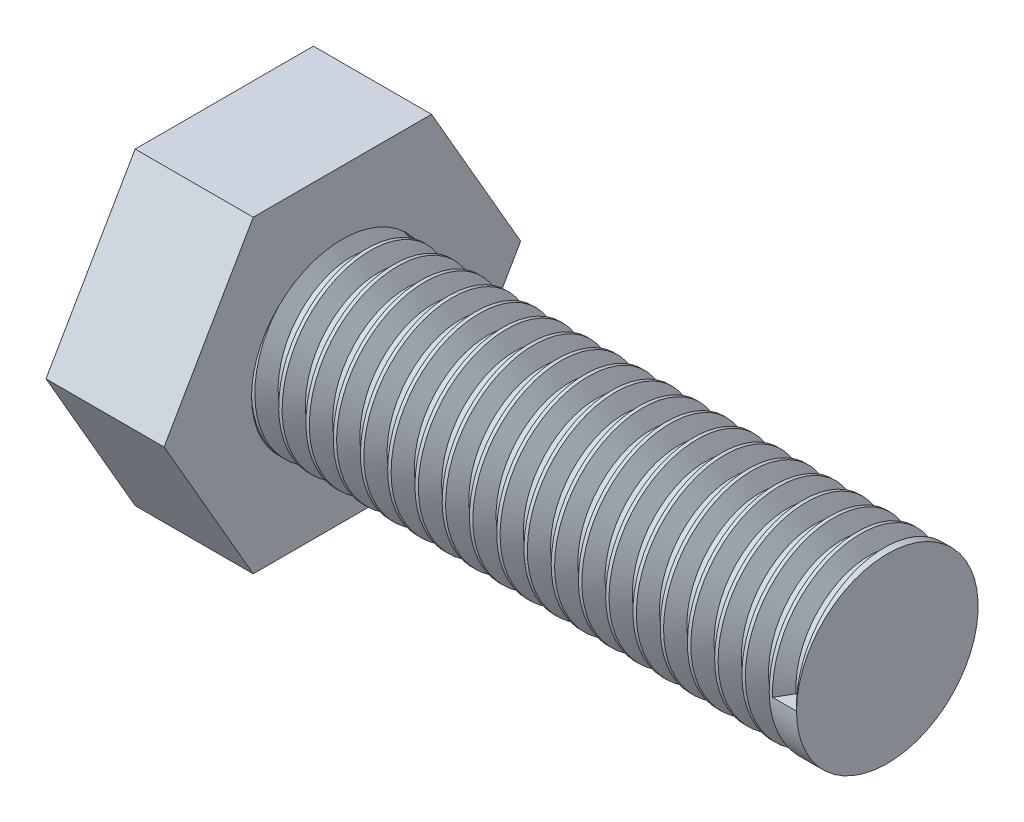
SolidWorks part; units mm, degrees
ref_plane "Front Plane" through (0, 0, 0) normal (0, 0, 1) x (1, 0, 0)
ref_plane "Top Plane" through (0, 0, 0) normal (0, 1, 0) x (1, 0, 0)
ref_plane "Right Plane" through (0, 0, 0) normal (1, 0, 0) x (0, 0, -1)
sketch "Sketch1" plane through (0, 0, 0) normal (0, 0, 1) x (1, 0, 0)
  line L0 (0, 0) -> (30, 0) construction
  line L1 (30, 0) -> (30, 5)
  line L2 (30, 5) -> (0, 5)
  line L6 (0, 0) -> (30, 0)
  line L7 (0, 5) -> (0, 0)
  dimension "D1" = 5
  dimension "D2" = 30
revolve "Revolve1" add sketch "Sketch1" angle 360 about L0
sketch "Sketch2" plane through (0, 0, 0) normal (-1, 0, 0) x (0, 0, 1)
  line L1 (9.815, 0) -> (4.9075, 8.5)
  line L2 (4.9075, 8.5) -> (-4.9075, 8.5)
  line L3 (-4.9075, 8.5) -> (-9.815, 0)
  line L4 (-9.815, 0) -> (-4.9075, -8.5)
  line L5 (-4.9075, -8.5) -> (4.9075, -8.5)
  line L6 (4.9075, -8.5) -> (9.815, 0)
  circle A0 centre (0, 0) radius 8.5 construction
  dimension "D1" = 17
extrude "Boss-Extrude1" add sketch "Sketch2" along normal blind 6.5
thread "Thread1" pitch 1.5 method cut profile "Thread Profile1" start angle 0, offset 0, length 0, pitch 1.5, diameter 10
ref_plane "Plane1" through (30, 0, 5) normal (0, -1, 0) x (0, 0, 1)
sketch "Thread Profile1" plane through (30, 0, 5) normal (0, -1, 0) x (0, 0, 1)
  line L0 (0, 0) -> (0, 1.5) construction
  line L11 (0, 0) -> (0, 1.3125)
  line L12 (0, 1.3125) -> (-0.8119, 0.8437)
  line L13 (-0.8119, 0.8437) -> (-0.8119, 0.4687)
  line L15 (-0.8119, 0.4687) -> (0, 0)
  line L17 (-0.8119, 0.6562) -> (0, 0.6562) construction
  point P2 (0, 0)
  dimension "Pitch" = 1.5
  dimension "Profile_Angle" = 60
  dimension "Profile_Land" = 0.375
  dimension "Profile_Height" = 0.8119
